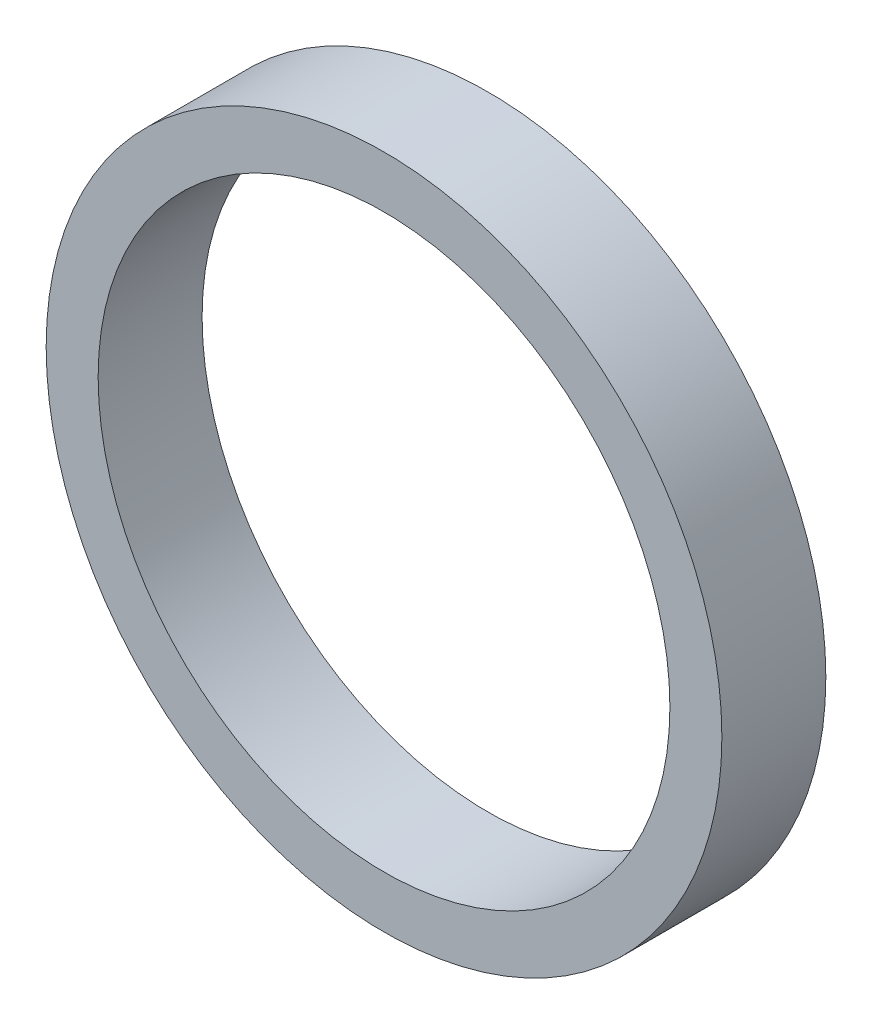
SolidWorks part; units mm, degrees
ref_plane "Спереди" through (0, 0, 0) normal (0, 0, 1) x (1, 0, 0)
ref_plane "Сверху" through (0, 0, 0) normal (0, 1, 0) x (1, 0, 0)
ref_plane "Справа" through (0, 0, 0) normal (1, 0, 0) x (0, 0, -1)
sketch "Эскиз1" plane through (0, 0, 0) normal (0, 0, 1) x (1, 0, 0)
  circle A0 centre (0, 0) radius 27.5 construction
  circle A1 centre (0, 0) radius 27.5
  circle A4 centre (0, 0) radius 32.5
  circle A5 centre (0, 0) radius 32.5
  dimension "D1" = 5
extrude "Бобышка-Вытянуть1" add sketch "Эскиз1" against normal blind 5 and the other way blind 5
